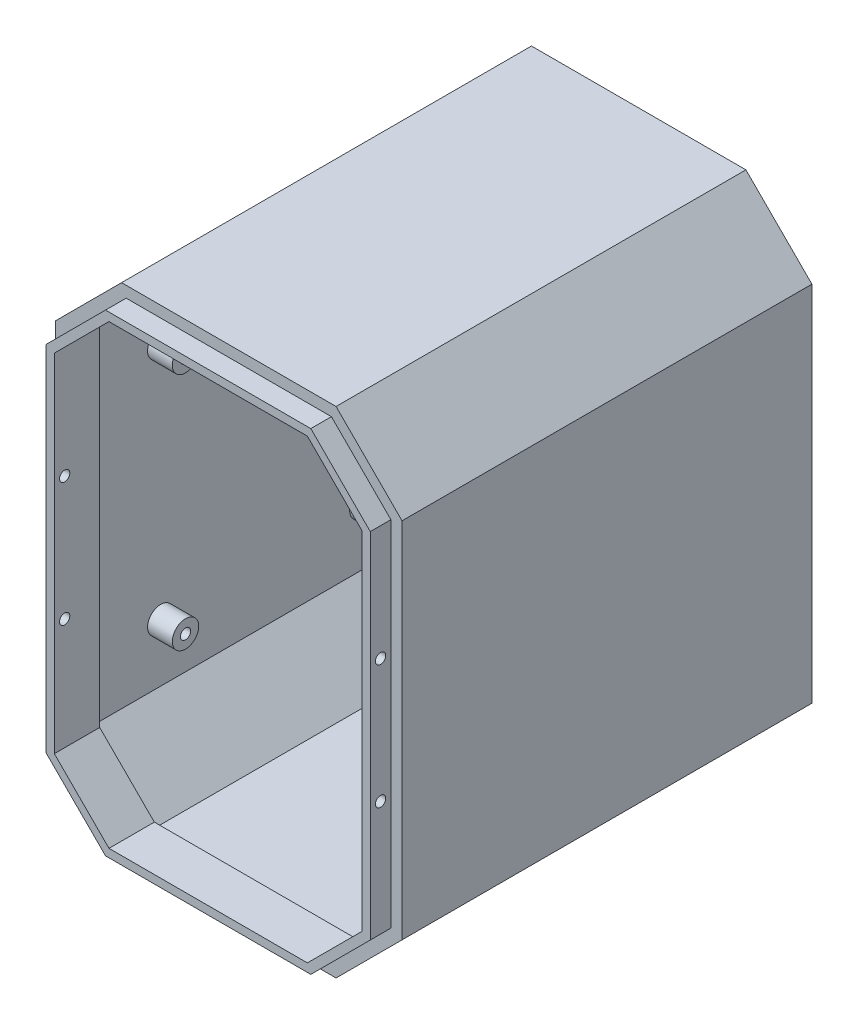
SolidWorks part; units mm, degrees
ref_plane "Front Plane" through (0, 0, 0) normal (0, 0, 1) x (1, 0, 0)
ref_plane "Top Plane" through (0, 0, 0) normal (0, 1, 0) x (1, 0, 0)
ref_plane "Right Plane" through (0, 0, 0) normal (1, 0, 0) x (0, 0, -1)
ref_plane "PZ_p68_625" through (0, 0, 68.625) normal (0, 0, 1) x (1, 0, 0)
sketch "S_prism1" plane through (0, 0, 68.625) normal (0, 0, 1) x (1, 0, 0)
  line L0 (42, -44) -> (42, 44)
  line L1 (42, 44) -> (26, 60)
  line L2 (26, 60) -> (-26, 60)
  line L3 (-26, 60) -> (-42, 44)
  line L4 (-42, 44) -> (-42, -44)
  line L5 (-42, -44) -> (-26, -60)
  line L6 (-26, -60) -> (26, -60)
  line L7 (26, -60) -> (42, -44)
  dimension "P1" = 42
  dimension "P2" = 44
  dimension "P3" = 42
  dimension "P4" = 44
  dimension "P5" = 26
  dimension "P6" = 60
  dimension "P7" = 26
  dimension "P8" = 60
  dimension "P9" = 42
  dimension "P10" = 44
  dimension "P11" = 42
  dimension "P12" = 44
  dimension "P13" = 26
  dimension "P14" = 60
  dimension "P15" = 26
  dimension "P16" = 60
extrude "Boss_1" add sketch "S_prism1" along normal blind 99.375
ref_plane "PZ_p71_125" through (0, 0, 71.125) normal (0, 0, 1) x (1, 0, 0)
sketch "S_pcut2" plane through (0, 0, 71.125) normal (0, 0, 1) x (1, 0, 0)
  line L0 (39.5, -42.9645) -> (39.5, 42.9645)
  line L1 (39.5, 42.9645) -> (24.9645, 57.5)
  line L2 (24.9645, 57.5) -> (-24.9645, 57.5)
  line L3 (-24.9645, 57.5) -> (-39.5, 42.9645)
  line L4 (-39.5, 42.9645) -> (-39.5, -42.9645)
  line L5 (-39.5, -42.9645) -> (-24.9645, -57.5)
  line L6 (-24.9645, -57.5) -> (24.9645, -57.5)
  line L7 (24.9645, -57.5) -> (39.5, -42.9645)
  dimension "P1" = 39.5
  dimension "P2" = 42.9645
  dimension "P3" = 39.5
  dimension "P4" = 42.9645
  dimension "P5" = 24.9645
  dimension "P6" = 57.5
  dimension "P7" = 24.9645
  dimension "P8" = 57.5
  dimension "P9" = 39.5
  dimension "P10" = 42.9645
  dimension "P11" = 39.5
  dimension "P12" = 42.9645
  dimension "P13" = 24.9645
  dimension "P14" = 57.5
  dimension "P15" = 24.9645
  dimension "P16" = 57.5
extrude "Cut_2" cut sketch "S_pcut2" along normal blind 96.975
sketch "S_cut3" plane through (0, 0, 71.125) normal (0, 0, 1) x (1, 0, 0)
  line L0 (-42.1, -16) -> (-39.4, -16)
  line L1 (-39.4, -16) -> (-39.4, 16)
  line L2 (-39.4, 16) -> (-42.1, 16)
  line L3 (-42.1, 16) -> (-42.1, -16)
  dimension "P1" = 42.1
  dimension "P2" = 16
  dimension "P3" = 39.4
  dimension "P4" = 16
  dimension "P5" = 39.4
  dimension "P6" = 16
  dimension "P7" = 42.1
  dimension "P8" = 16
extrude "Pocket_3" cut sketch "S_cut3" along normal blind 14
ref_plane "PX_m42_100" through (-42.1, 0, 0) normal (1, 0, 0) x (0, 0, -1)
sketch "S_hole4" plane through (-42.1, 0, 0) normal (1, 0, 0) x (0, 0, -1)
  circle A0 centre (-88, 0) radius 6
  dimension "D1_S_hole4" = 12
  dimension "P2" = 88
extrude "Hole_4" cut sketch "S_hole4" along normal blind 2.7
ref_plane "PZ_p68_525" through (0, 0, 68.525) normal (0, 0, 1) x (1, 0, 0)
sketch "S_hole5" plane through (0, 0, 68.525) normal (0, 0, 1) x (1, 0, 0)
  circle A0 centre (0, -25) radius 1.6
  dimension "D1_S_hole5" = 3.2
  dimension "P2" = 25
extrude "Hole_5" cut sketch "S_hole5" along normal blind 2.7
sketch "S_hole6" plane through (0, 0, 68.525) normal (0, 0, 1) x (1, 0, 0)
  circle A0 centre (0, 25) radius 1.6
  dimension "D1_S_hole6" = 3.2
  dimension "P2" = 25
extrude "Hole_6" cut sketch "S_hole6" along normal blind 2.7
sketch "S_hole7" plane through (0, 0, 68.525) normal (0, 0, 1) x (1, 0, 0)
  circle A0 centre (28, -25) radius 1.6
  dimension "D1_S_hole7" = 3.2
  dimension "P2" = 28
  dimension "P3" = 25
extrude "Hole_7" cut sketch "S_hole7" along normal blind 2.7
sketch "S_hole8" plane through (0, 0, 68.525) normal (0, 0, 1) x (1, 0, 0)
  circle A0 centre (28, 25) radius 1.6
  dimension "D1_S_hole8" = 3.2
  dimension "P2" = 28
  dimension "P3" = 25
extrude "Hole_8" cut sketch "S_hole8" along normal blind 2.7
ref_plane "PZ_p162_000" through (0, 0, 162) normal (0, 0, 1) x (1, 0, 0)
sketch "S_prism9" plane through (0, 0, 162) normal (0, 0, 1) x (1, 0, 0)
  line L0 (40, -43.1716) -> (40, 43.1716)
  line L1 (40, 43.1716) -> (25.1716, 58)
  line L2 (25.1716, 58) -> (-25.1716, 58)
  line L3 (-25.1716, 58) -> (-40, 43.1716)
  line L4 (-40, 43.1716) -> (-40, -43.1716)
  line L5 (-40, -43.1716) -> (-25.1716, -58)
  line L6 (-25.1716, -58) -> (25.1716, -58)
  line L7 (25.1716, -58) -> (40, -43.1716)
  dimension "P1" = 40
  dimension "P2" = 43.1716
  dimension "P3" = 40
  dimension "P4" = 43.1716
  dimension "P5" = 25.1716
  dimension "P6" = 58
  dimension "P7" = 25.1716
  dimension "P8" = 58
  dimension "P9" = 40
  dimension "P10" = 43.1716
  dimension "P11" = 40
  dimension "P12" = 43.1716
  dimension "P13" = 25.1716
  dimension "P14" = 58
  dimension "P15" = 25.1716
  dimension "P16" = 58
extrude "Boss_9" add sketch "S_prism9" along normal blind 6
ref_plane "PZ_p167_900" through (0, 0, 167.9) normal (0, 0, 1) x (1, 0, 0)
sketch "S_prism10" plane through (0, 0, 167.9) normal (0, 0, 1) x (1, 0, 0)
  line L0 (39.3, -42.8816) -> (39.3, 42.8816)
  line L1 (39.3, 42.8816) -> (24.8816, 57.3)
  line L2 (24.8816, 57.3) -> (-24.8816, 57.3)
  line L3 (-24.8816, 57.3) -> (-39.3, 42.8816)
  line L4 (-39.3, 42.8816) -> (-39.3, -42.8816)
  line L5 (-39.3, -42.8816) -> (-24.8816, -57.3)
  line L6 (-24.8816, -57.3) -> (24.8816, -57.3)
  line L7 (24.8816, -57.3) -> (39.3, -42.8816)
  dimension "P1" = 39.3
  dimension "P2" = 42.8816
  dimension "P3" = 39.3
  dimension "P4" = 42.8816
  dimension "P5" = 24.8816
  dimension "P6" = 57.3
  dimension "P7" = 24.8816
  dimension "P8" = 57.3
  dimension "P9" = 39.3
  dimension "P10" = 42.8816
  dimension "P11" = 39.3
  dimension "P12" = 42.8816
  dimension "P13" = 24.8816
  dimension "P14" = 57.3
  dimension "P15" = 24.8816
  dimension "P16" = 57.3
extrude "Boss_10" add sketch "S_prism10" along normal blind 5.1
ref_plane "PX_m40_000" through (-40, 0, 0) normal (1, 0, 0) x (0, 0, -1)
sketch "S_cyl11" plane through (-40, 0, 0) normal (1, 0, 0) x (0, 0, -1)
  circle A0 centre (-96, -29) radius 3.2
  dimension "D1_S_cyl11" = 6.4
  dimension "P2" = 96
  dimension "P3" = 29
extrude "Boss_11" add sketch "S_cyl11" along normal blind 6.5
sketch "S_cyl12" plane through (-40, 0, 0) normal (1, 0, 0) x (0, 0, -1)
  circle A0 centre (-145, -29) radius 3.2
  dimension "D1_S_cyl12" = 6.4
  dimension "P2" = 145
  dimension "P3" = 29
extrude "Boss_12" add sketch "S_cyl12" along normal blind 6.5
sketch "S_cyl13" plane through (-40, 0, 0) normal (1, 0, 0) x (0, 0, -1)
  circle A0 centre (-96, 29) radius 3.2
  dimension "D1_S_cyl13" = 6.4
  dimension "P2" = 96
  dimension "P3" = 29
extrude "Boss_13" add sketch "S_cyl13" along normal blind 6.5
sketch "S_cyl14" plane through (-40, 0, 0) normal (1, 0, 0) x (0, 0, -1)
  circle A0 centre (-145, 29) radius 3.2
  dimension "D1_S_cyl14" = 6.4
  dimension "P2" = 145
  dimension "P3" = 29
extrude "Boss_14" add sketch "S_cyl14" along normal blind 6.5
ref_plane "PZ_p161_900" through (0, 0, 161.9) normal (0, 0, 1) x (1, 0, 0)
sketch "S_pcut15" plane through (0, 0, 161.9) normal (0, 0, 1) x (1, 0, 0)
  line L0 (37.3, -42.0532) -> (37.3, 42.0532)
  line L1 (37.3, 42.0532) -> (24.0532, 55.3)
  line L2 (24.0532, 55.3) -> (-24.0532, 55.3)
  line L3 (-24.0532, 55.3) -> (-37.3, 42.0532)
  line L4 (-37.3, 42.0532) -> (-37.3, -42.0532)
  line L5 (-37.3, -42.0532) -> (-24.0532, -55.3)
  line L6 (-24.0532, -55.3) -> (24.0532, -55.3)
  line L7 (24.0532, -55.3) -> (37.3, -42.0532)
  dimension "P1" = 37.3
  dimension "P2" = 42.0532
  dimension "P3" = 37.3
  dimension "P4" = 42.0532
  dimension "P5" = 24.0532
  dimension "P6" = 55.3
  dimension "P7" = 24.0532
  dimension "P8" = 55.3
  dimension "P9" = 37.3
  dimension "P10" = 42.0532
  dimension "P11" = 37.3
  dimension "P12" = 42.0532
  dimension "P13" = 24.0532
  dimension "P14" = 55.3
  dimension "P15" = 24.0532
  dimension "P16" = 55.3
extrude "Cut_15" cut sketch "S_pcut15" along normal blind 11.2
ref_plane "PX_p37_100" through (37.1, 0, 0) normal (1, 0, 0) x (0, 0, -1)
sketch "S_hole16" plane through (37.1, 0, 0) normal (1, 0, 0) x (0, 0, -1)
  circle A0 centre (-170.5, -15) radius 1.25
  dimension "D1_S_hole16" = 2.5
  dimension "P2" = 170.5
  dimension "P3" = 15
extrude "Hole_16" cut sketch "S_hole16" along normal blind 2.7
sketch "S_hole17" plane through (37.1, 0, 0) normal (1, 0, 0) x (0, 0, -1)
  circle A0 centre (-170.5, 15) radius 1.25
  dimension "D1_S_hole17" = 2.5
  dimension "P2" = 170.5
  dimension "P3" = 15
extrude "Hole_17" cut sketch "S_hole17" along normal blind 2.7
ref_plane "PX_m39_800" through (-39.8, 0, 0) normal (1, 0, 0) x (0, 0, -1)
sketch "S_hole18" plane through (-39.8, 0, 0) normal (1, 0, 0) x (0, 0, -1)
  circle A0 centre (-170.5, -15) radius 1.25
  dimension "D1_S_hole18" = 2.5
  dimension "P2" = 170.5
  dimension "P3" = 15
extrude "Hole_18" cut sketch "S_hole18" along normal blind 2.7
sketch "S_hole19" plane through (-39.8, 0, 0) normal (1, 0, 0) x (0, 0, -1)
  circle A0 centre (-170.5, 15) radius 1.25
  dimension "D1_S_hole19" = 2.5
  dimension "P2" = 170.5
  dimension "P3" = 15
extrude "Hole_19" cut sketch "S_hole19" along normal blind 2.7
ref_plane "PX_m39_500" through (-39.5, 0, 0) normal (1, 0, 0) x (0, 0, -1)
sketch "S_hole20" plane through (-39.5, 0, 0) normal (1, 0, 0) x (0, 0, -1)
  circle A0 centre (-96, -29) radius 1.25
  dimension "D1_S_hole20" = 2.5
  dimension "P2" = 96
  dimension "P3" = 29
extrude "Hole_20" cut sketch "S_hole20" along normal blind 6.1
sketch "S_hole21" plane through (-39.5, 0, 0) normal (1, 0, 0) x (0, 0, -1)
  circle A0 centre (-145, -29) radius 1.25
  dimension "D1_S_hole21" = 2.5
  dimension "P2" = 145
  dimension "P3" = 29
extrude "Hole_21" cut sketch "S_hole21" along normal blind 6.1
sketch "S_hole22" plane through (-39.5, 0, 0) normal (1, 0, 0) x (0, 0, -1)
  circle A0 centre (-96, 29) radius 1.25
  dimension "D1_S_hole22" = 2.5
  dimension "P2" = 96
  dimension "P3" = 29
extrude "Hole_22" cut sketch "S_hole22" along normal blind 6.1
sketch "S_hole23" plane through (-39.5, 0, 0) normal (1, 0, 0) x (0, 0, -1)
  circle A0 centre (-145, 29) radius 1.25
  dimension "D1_S_hole23" = 2.5
  dimension "P2" = 145
  dimension "P3" = 29
extrude "Hole_23" cut sketch "S_hole23" along normal blind 6.1
equation "\"plate_t\" = 3"
equation "\"clearance\" = 0.4"
